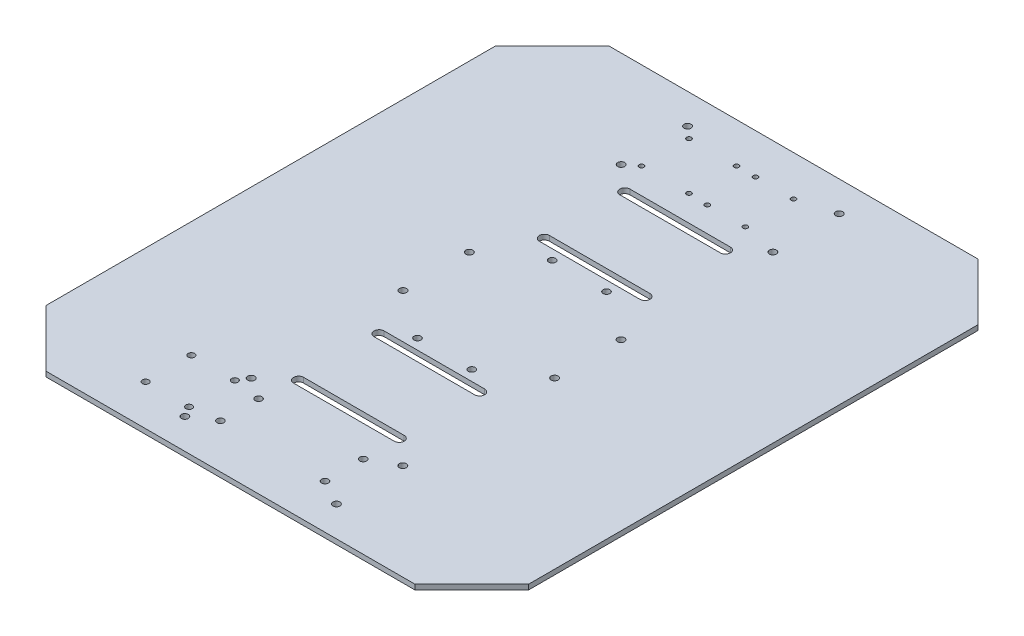
SolidWorks part; units mm, degrees
ref_plane "Front Plane" through (0, 0, 0) normal (0, 0, 1) x (1, 0, 0)
ref_plane "Top Plane" through (0, 0, 0) normal (0, 1, 0) x (1, 0, 0)
ref_plane "Right Plane" through (0, 0, 0) normal (1, 0, 0) x (0, 0, -1)
sketch "Sketch1" plane through (0, 0, 0) normal (0, 1, 0) x (1, 0, 0)
  line L0 (-121.2861, 87.138) -> (-85.365, 123.059)
  line L1 (-121.2861, 123.059) -> (183.5139, 123.059)
  line L2 (-121.2861, 123.059) -> (-121.2861, -232.541)
  line L3 (-121.2861, -232.541) -> (183.5139, -232.541)
  line L4 (183.5139, 123.059) -> (183.5139, -232.541)
  line L5 (31.1139, 95.069) -> (31.1139, -294.9418) construction
  line L6 (-146.0448, -54.741) -> (218.038, -54.741) construction
  line L7 (183.5139, 87.138) -> (147.5929, 123.059)
  line L8 (183.5139, -196.62) -> (147.5929, -232.541)
  line L9 (-121.2861, -196.62) -> (-85.365, -232.541)
  circle A0 centre (-16.7651, 104.009) radius 2.2225
  circle A1 centre (78.9929, 104.009) radius 2.2225
  circle A2 centre (-16.7651, 62.099) radius 2.2225
  circle A3 centre (78.9929, 62.099) radius 2.2225
  circle A4 centre (-16.7651, -171.581) radius 2.2225
  circle A5 centre (78.9929, -171.581) radius 2.2225
  circle A6 centre (78.9929, -213.491) radius 2.2225
  circle A7 centre (-16.7651, -213.491) radius 2.2225
  circle A8 centre (-16.7651, -33.786) radius 2.2225
  circle A9 centre (78.9929, -33.786) radius 2.2225
  circle A10 centre (78.9929, -75.696) radius 2.2225
  circle A11 centre (-16.7651, -75.696) radius 2.2225
  point P8 (31.1139, 123.059)
  point P11 (-121.2861, -54.741)
  dimension "D6" = 95.758
  dimension "D13" = 4.445
  dimension "D1" = 304.8
  dimension "D2" = 355.6
  dimension "D3" = 45
  dimension "D4" = 50.8
  dimension "D5" = 41.91
  dimension "D7" = 104.521
  dimension "D8" = 19.05
  dimension "D9" = 41.91
  dimension "D10" = 20.955
  dimension "D11" = 95.758
  dimension "D12" = 47.879
extrude "Boss-Extrude1" add sketch "Sketch1" along normal blind 3.175 contours L2 L9 L3 L8 L4 L7 L1 L0 region at (31.1139, 0, 54.741)
sketch "Sketch2" plane through (0, 3.175, 0) normal (0, 1, 0) x (1, 0, 0)
  line L0 (31.1139, 123.059) -> (31.1139, -287.8465) construction
  line L1 (-85.365, 123.059) -> (147.5929, 123.059) construction
  line L2 (183.5139, -54.741) -> (-158.2106, -54.741) construction
  line L3 (183.5139, 87.138) -> (183.5139, -196.62) construction
  circle A0 centre (13.8419, -12.069) radius 2.159
  circle A1 centre (48.1319, -12.069) radius 2.159
  circle A2 centre (13.8419, -97.159) radius 2.159
  circle A3 centre (48.1319, -97.159) radius 2.159
  dimension "D5" = 4.318
  dimension "D6" = 4.318
  dimension "D7" = 4.318
  dimension "D8" = 4.318
  dimension "D1" = 17.272
  dimension "D2" = 34.29
  dimension "D3" = 85.09
  dimension "D4" = 42.672
extrude "Cut-Extrude1" cut sketch "Sketch2" against normal through all
sketch "Sketch4" plane through (0, 3.175, 0) normal (0, 1, 0) x (1, 0, 0)
  line L0 (-0.6361, 48.256) -> (62.8639, 48.256) construction
  line L1 (-0.6361, 51.431) -> (62.8639, 51.431)
  line L2 (-0.6361, 45.081) -> (62.8639, 45.081)
  line L3 (-0.6361, -2.544) -> (62.8639, -2.544) construction
  line L4 (-0.6361, 0.631) -> (62.8639, 0.631)
  line L5 (-0.6361, -5.719) -> (62.8639, -5.719)
  line L6 (31.1139, 123.059) -> (31.1139, -75.2432) construction
  line L7 (-85.365, 123.059) -> (147.5929, 123.059) construction
  line L8 (-121.2861, -54.741) -> (257.7387, -54.741) construction
  line L9 (-121.2861, 87.138) -> (-121.2861, -196.62) construction
  line L10 (31.1139, -232.541) -> (31.1139, -34.2388) construction
  line L11 (-0.6361, -106.938) -> (62.8639, -106.938) construction
  line L12 (-0.6361, -110.113) -> (62.8639, -110.113)
  line L13 (-0.6361, -103.763) -> (62.8639, -103.763)
  line L14 (-0.6361, -157.738) -> (62.8639, -157.738) construction
  line L15 (-0.6361, -160.913) -> (62.8639, -160.913)
  line L16 (-0.6361, -154.563) -> (62.8639, -154.563)
  arc A0 (-0.6361, 51.431) -> (-0.6361, 45.081) centre (-0.6361, 48.256) ccw
  arc A1 (62.8639, 45.081) -> (62.8639, 51.431) centre (62.8639, 48.256) ccw
  arc A2 (-0.6361, 0.631) -> (-0.6361, -5.719) centre (-0.6361, -2.544) ccw
  arc A3 (62.8639, -5.719) -> (62.8639, 0.631) centre (62.8639, -2.544) ccw
  circle A4 centre (48.1319, -12.069) radius 2.159 construction
  arc A5 (-0.6361, -110.113) -> (-0.6361, -103.763) centre (-0.6361, -106.938) cw
  arc A6 (62.8639, -103.763) -> (62.8639, -110.113) centre (62.8639, -106.938) cw
  arc A7 (-0.6361, -160.913) -> (-0.6361, -154.563) centre (-0.6361, -157.738) cw
  arc A8 (62.8639, -154.563) -> (62.8639, -160.913) centre (62.8639, -157.738) cw
  point P2 (31.1139, 48.256)
  point P7 (31.1139, -2.544)
  point P28 (31.1139, -106.938)
  point P35 (31.1139, -157.738)
  dimension "D1" = 63.5
  dimension "D2" = 63.5
  dimension "D3" = 6.35
  dimension "D4" = 6.35
  dimension "D5" = 44.45
  dimension "D6" = 6.35
extrude "Cut-Extrude2" cut sketch "Sketch4" against normal through all
sketch "Sketch7" plane through (0, 3.175, 0) normal (0, 1, 0) x (1, 0, 0)
  line L1 (-121.2861, 87.138) -> (-121.2861, -196.62) construction
  line L3 (-85.365, 123.059) -> (147.5929, 123.059) construction
  circle A0 centre (-9.5261, 67.687) radius 1.524
  circle A1 centre (20.4459, 67.687) radius 1.524
  circle A2 centre (-9.5261, 97.659) radius 1.524
  circle A3 centre (20.4459, 97.659) radius 1.524
  dimension "D1" = 3.048
  dimension "D2" = 3.048
  dimension "D3" = 29.972
  dimension "D4" = 29.972
  dimension "D5" = 25.4
  dimension "D6" = 111.76
extrude "Cut-Extrude3" cut sketch "Sketch7" against normal through all
sketch "Sketch8" plane through (0, 3.175, 0) normal (0, 1, 0) x (1, 0, 0)
  line L1 (183.5139, 87.138) -> (183.5139, -196.62) construction
  line L2 (-85.365, 123.059) -> (147.5929, 123.059) construction
  circle A0 centre (32.5135, 67.179) radius 1.524
  circle A1 centre (32.5135, 97.659) radius 1.524
  circle A2 centre (56.5139, 67.179) radius 1.524
  circle A3 centre (56.5139, 97.659) radius 1.524
  dimension "D1" = 3.048
  dimension "D2" = 30.48
  dimension "D3" = 24.0005
  dimension "D4" = 25.4
  dimension "D5" = 127
extrude "Cut-Extrude4" cut sketch "Sketch8" against normal through all and the other way through all
sketch "Sketch9" plane through (0, 0, 0) normal (0, -1, 0) x (-1, 0, 0)
  line L0 (85.365, -232.541) -> (-147.5929, -232.541) construction
  line L1 (121.2861, 87.138) -> (121.2861, -196.62) construction
  circle A0 centre (48.1341, -206.887) radius 2.032
  circle A1 centre (20.7021, -206.887) radius 2.032
  circle A2 centre (48.1341, -177.931) radius 2.032
  circle A3 centre (20.7021, -177.931) radius 2.032
  dimension "D1" = 4.064
  dimension "D2" = 27.432
  dimension "D3" = 28.956
  dimension "D4" = 25.654
  dimension "D5" = 73.152
extrude "Cut-Extrude5" cut sketch "Sketch9" against normal through all
sketch "Sketch10" plane through (0, 0, 0) normal (0, -1, 0) x (1, 0, 0)
  line L0 (-85.365, 232.541) -> (147.5929, 232.541) construction
  line L1 (183.5139, -87.138) -> (183.5139, 196.62) construction
  circle A0 centre (-3.1761, 204.601) radius 2.159
  circle A1 centre (62.8639, 204.601) radius 2.159
  circle A2 centre (-3.1761, 180.471) radius 2.159
  circle A3 centre (62.8639, 180.471) radius 2.159
  dimension "D1" = 4.318
  dimension "D2" = 66.04
  dimension "D4" = 27.94
  dimension "D6" = 4.318
  dimension "D7" = 4.318
  dimension "D8" = 4.318
  dimension "D3" = 24.13
  dimension "D5" = 120.65
extrude "Cut-Extrude6" cut sketch "Sketch10" against normal through all
